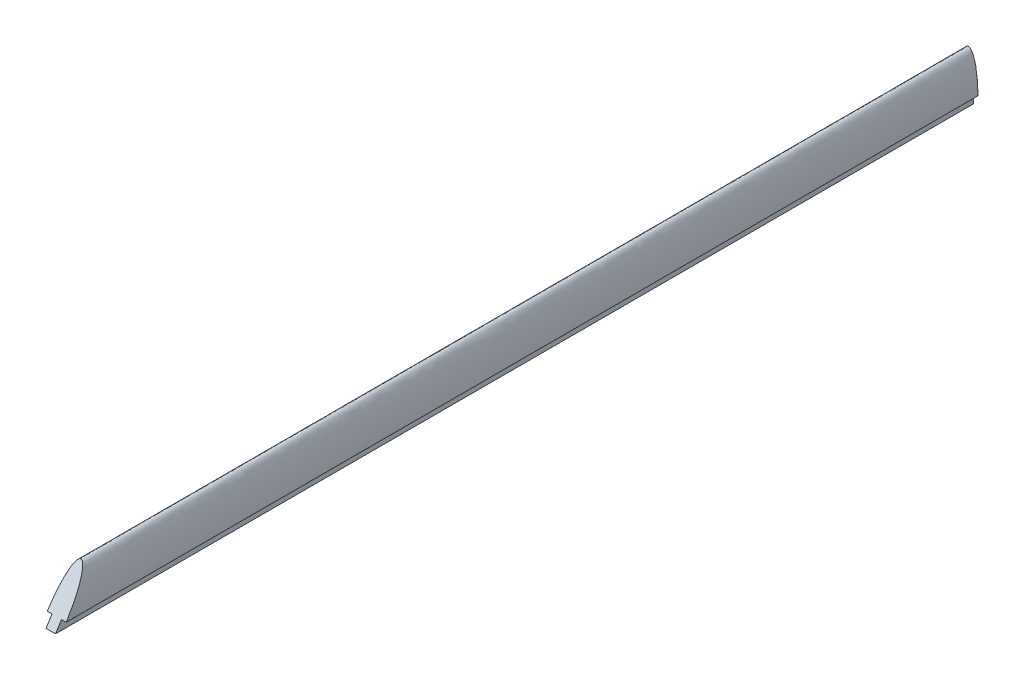
SolidWorks part; units mm, degrees
ref_plane "Front Plane" through (0, 0, 0) normal (0, 0, 1) x (1, 0, 0)
ref_plane "Top Plane" through (0, 0, 0) normal (0, 1, 0) x (1, 0, 0)
ref_plane "Right Plane" through (0, 0, 0) normal (1, 0, 0) x (0, 0, -1)
sketch "Cross Section" plane through (0, 0, 0) normal (0, 0, 1) x (1, 0, 0)
  line L0 (10, 0) -> (20, 0) construction
  line L1 (0, 80) -> (0, 0) construction
  line L2 (10, 0) -> (20, 0)
  line L4 (-10, 0) -> (-10, -20)
  line L5 (-10, -20) -> (10, -20)
  line L6 (10, 0) -> (10, -20)
  line L7 (-10, 0) -> (10, -20) construction
  line L8 (-10, -20) -> (10, 0) construction
  line L10 (-20, 0) -> (-10, 0)
  line L11 (-10, 0) -> (10, 0) construction
  ellipse E0 centre (0, 0) end of major axis (0, -80) minor radius 20 (20, 0) -> (-20, 0) ccw
  point P2 (0, -10)
  dimension "D1" = 40
  dimension "D2" = 80
  dimension "D3" = 10
extrude "Profile Extrude" add sketch "Cross Section" along normal blind 2000
sketch "Flush Support Cut Sketch" plane through (0, 0, 0) normal (1, 0, 0) x (0, 0, -1)
  line L0 (-2000, -126.1238) -> (-1869.2562, 80)
  line L1 (-1869.2562, 80) -> (-2000, 80)
  line L2 (-2000, 80) -> (-2000, -126.1238)
  line L3 (-2000, 80) -> (-2000, 0) construction
  line L4 (0, 80) -> (-2000, 80) construction
  line L5 (-1920, 0) -> (-1989.8893, -110.1839) construction
extrude "Flush Support Cut" cut sketch "Flush Support Cut Sketch" against normal up to surface and the other way up to surface up to face at (0, 40, 1000) other way up to face at (0, 40, 1000)
